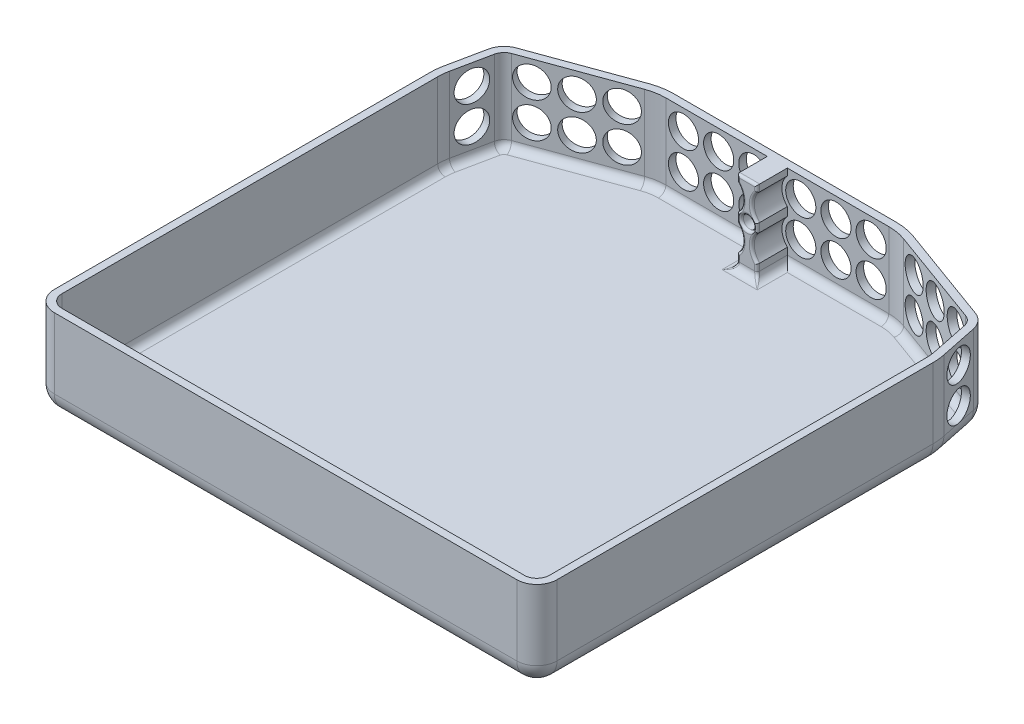
SolidWorks part; units mm, degrees
material "ABS"
ref_plane "Front Plane" through (0, 0, 0) normal (0, 0, 1) x (1, 0, 0)
ref_plane "Top Plane" through (0, 0, 0) normal (0, 1, 0) x (1, 0, 0)
ref_plane "Right Plane" through (0, 0, 0) normal (1, 0, 0) x (0, 0, -1)
sketch "Sketch1" plane through (0, 0, 0) normal (0, 1, 0) x (1, 0, 0)
  line L0 (-100, 0) -> (0, 0) construction
  line L1 (0, 118.6458) -> (-48.563, 118.6458)
  line L2 (-100, 80) -> (-100, -80)
  line L3 (-100, -80) -> (0, -80)
  line L4 (-48.563, 118.6458) -> (-95.5476, 101.5447)
  line L5 (0, 118.6458) -> (0, -80)
  line L7 (-100, 80) -> (-95.5476, 101.5447)
  line L8 (0, -80) -> (0, 118.6458) construction
  point P0 (0, 0)
  dimension "D3" = 191.676
  dimension "D6" = 50
  dimension "D1" = 22
  dimension "D2" = 160
  dimension "D4" = 200
  dimension "D5" = 100
extrude "Boss-Extrude1" add sketch "Sketch1" along normal blind 36
fillet "Fillet4" radius 8 1 edges at (-100, 18, 80)
fillet "Fillet5" radius 24 1 edges at (-100, 18, -80)
fillet "Fillet6" radius 8 1 edges at (-95.5476, 18, -101.5447)
fillet "Fillet7" radius 24 1 edges at (-48.563, 18, -118.6458)
sketch "Sketch2" plane through (0, 0, -118.6458) normal (0, 0, -1) x (-1, 0, 0)
  line L0 (44.3311, 0) -> (44.3311, 36) construction
  line L1 (0, 36) -> (44.3311, 36) construction
  line L2 (9.3311, 14) -> (9.3311, 28) construction
  line L3 (29.3311, 28) -> (31.3311, 28) construction
  line L4 (9.3311, 21) -> (0, 21) construction
  line L5 (0, 36) -> (0, 0) construction
  line L6 (0, 0) -> (44.3311, 0) construction
  circle A0 centre (37.3311, 28) radius 6
  circle A1 centre (23.3311, 28) radius 6
  circle A2 centre (9.3311, 28) radius 6
  circle A3 centre (23.3311, 14) radius 6
  circle A4 centre (9.3311, 14) radius 6
  circle A5 centre (37.3311, 14) radius 6
  circle A6 centre (0, 21) radius 2.5
  dimension "D1" = 12
  dimension "D6" = 5
  dimension "D2" = 7
  dimension "D3" = 8
  dimension "D7" = 21
  dimension "D8" = 14
  dimension "D4" = 3
  dimension "D5" = 2
extrude "Cut-Extrude1" cut sketch "Sketch2" against normal blind 20
sketch "Sketch3" plane through (-43.8128, 0, -120.3747) normal (-0.342, 0, -0.9397) x (-0.9397, 0, 0.342)
  line L0 (9.2869, 36) -> (50.591, 36) construction
  line L1 (9.2869, 36) -> (9.2869, 0) construction
  circle A0 centre (16.2869, 28) radius 6
  circle A1 centre (30.2869, 28) radius 6
  circle A2 centre (44.2869, 28) radius 6
  circle A3 centre (30.2869, 14) radius 6
  circle A4 centre (44.2869, 14) radius 6
  circle A5 centre (16.2869, 14) radius 6
  dimension "D1" = 12
  dimension "D2" = 8
  dimension "D3" = 7
  dimension "D6" = 21
  dimension "D7" = 22
  dimension "D4" = 3
  dimension "D5" = 2
extrude "Cut-Extrude2" cut sketch "Sketch3" against normal blind 10
sketch "Sketch4" plane through (-111.7597, 0, -23.096) normal (-0.9793, 0, -0.2024) x (-0.2024, 0, 0.9793)
  line L0 (-68.1013, 36) -> (-68.1013, 0) construction
  line L1 (-75.6423, 36) -> (-60.5604, 36) construction
  line L2 (-75.6423, 0) -> (-60.5604, 0) construction
  circle A0 centre (-68.1013, 28) radius 6
  circle A1 centre (-68.1013, 14) radius 6
  dimension "D1" = 12
  dimension "D3" = 2
  dimension "D2" = 8
  dimension "D4" = 22
extrude "Cut-Extrude3" cut sketch "Sketch4" against normal blind 10
mirror "Mirror2" of "Cut-Extrude3", "Cut-Extrude2", "Cut-Extrude1", "Fillet7", "Fillet6", "Fillet5", "Fillet4", "Boss-Extrude1"
fillet "Fillet3" radius 8 16 edges at (-100, 0, -2.773) (0, 0, 80) (0, 0, -118.6458) (-71.9462, 0, -110.135) (-97.9772, 0, -89.7881) (-48.4987, 0, -118.2811) (-94.6691, 0, -100.7854) (-99.8755, 0, -79.9873) (-97.6569, 0, 77.6569) (97.6569, 0, 77.6569) (100, 0, -2.773) (99.8755, 0, -79.9873) (97.9772, 0, -89.7881) (94.6691, 0, -100.7854) (71.9462, 0, -110.135) (48.4987, 0, -118.2811)
sketch "Sketch5" plane through (0, 36, 0) normal (0, 1, 0) x (1, 0, 0)
  line L0 (0, 103.6458) -> (0, 118.6458) construction
  line L1 (44.3311, 118.6458) -> (-44.3311, 118.6458) construction
  line L2 (4, 115.6458) -> (4, 103.6458)
  line L3 (4, 103.6458) -> (-4, 103.6458)
  line L4 (-4, 115.6458) -> (-4, 103.6458)
  line L7 (-4, 115.6458) -> (-44.3311, 115.6458)
  line L16 (90.3267, 100.2525) -> (51.5136, 114.3793)
  line L17 (44.3311, 115.6458) -> (-44.3311, 115.6458)
  line L18 (-51.5136, 114.3793) -> (-90.3267, 100.2525)
  line L19 (-93.5131, 96.5659) -> (-96.5654, 81.796)
  line L20 (-97, 77.546) -> (-97, -72)
  line L21 (-92, -77) -> (92, -77)
  line L22 (97, -72) -> (97, 77.546)
  line L23 (96.5654, 81.796) -> (93.5131, 96.5659)
  line L24 (90.3267, 100.2525) -> (51.5136, 114.3793)
  line L25 (44.3311, 115.6458) -> (4, 115.6458)
  line L26 (-51.5136, 114.3793) -> (-90.3267, 100.2525)
  line L27 (-93.5131, 96.5659) -> (-96.5654, 81.796)
  line L28 (-97, 77.546) -> (-97, -72)
  line L29 (-92, -77) -> (92, -77)
  line L30 (97, -72) -> (97, 77.546)
  line L31 (96.5654, 81.796) -> (93.5131, 96.5659)
  arc A16 (51.5136, 114.3793) -> (44.3311, 115.6458) centre (44.3311, 94.6458) ccw
  arc A17 (-44.3311, 115.6458) -> (-51.5136, 114.3793) centre (-44.3311, 94.6458) ccw
  arc A18 (-90.3267, 100.2525) -> (-93.5131, 96.5659) centre (-88.6166, 95.554) ccw
  arc A19 (-96.5654, 81.796) -> (-97, 77.546) centre (-76, 77.546) ccw
  arc A20 (-97, -72) -> (-92, -77) centre (-92, -72) ccw
  arc A21 (92, -77) -> (97, -72) centre (92, -72) ccw
  arc A22 (97, 77.546) -> (96.5654, 81.796) centre (76, 77.546) ccw
  arc A23 (93.5131, 96.5659) -> (90.3267, 100.2525) centre (88.6166, 95.554) ccw
  arc A24 (51.5136, 114.3793) -> (44.3311, 115.6458) centre (44.3311, 94.6458) ccw
  arc A25 (-44.3311, 115.6458) -> (-51.5136, 114.3793) centre (-44.3311, 94.6458) ccw
  arc A26 (-90.3267, 100.2525) -> (-93.5131, 96.5659) centre (-88.6166, 95.554) ccw
  arc A27 (-96.5654, 81.796) -> (-97, 77.546) centre (-76, 77.546) ccw
  arc A28 (-97, -72) -> (-92, -77) centre (-92, -72) ccw
  arc A29 (92, -77) -> (97, -72) centre (92, -72) ccw
  arc A30 (97, 77.546) -> (96.5654, 81.796) centre (76, 77.546) ccw
  arc A31 (93.5131, 96.5659) -> (90.3267, 100.2525) centre (88.6166, 95.554) ccw
  dimension "D2" = 12
  dimension "D3" = 8
  dimension "D1" = 3
extrude "Cut-Extrude4" cut sketch "Sketch5" against normal offset from surface (33 mm away) 3 up to face at (0, 0, -67.0764)
fillet "Fillet8" radius 3 20 edges at (95.0393, 3, -89.181) (96.8911, 3, -79.6821) (97, 3, -2.773) (95.5355, 3, 75.5355) (0, 3, 77) (-95.5355, 3, 75.5355) (-97, 3, -2.773) (-96.8911, 3, -79.6821) (-95.0393, 3, -89.181) (-92.3994, 3, -98.8236) (-70.9201, 3, -107.3159) (-47.9777, 3, -115.3267) (24.1656, 3, -115.6458) (47.9777, 3, -115.3267) (70.9201, 3, -107.3159) (92.3994, 3, -98.8236) (-24.1656, 3, -115.6458) (-4, 3, -109.6458) (0, 3, -103.6458) (4, 3, -109.6458)
sketch "Sketch6" plane through (0, 0, -115.6458) normal (0, 0, 1) x (1, 0, 0)
  arc A0 (-6.6385, 21) -> (-12.0237, 21) centre (-9.3311, 28) ccw
  arc A1 (-4, 30.753) -> (-4, 25.247) centre (-9.3311, 28) ccw construction
  arc A2 (-12.0237, 21) -> (-6.6385, 21) centre (-9.3311, 14) ccw
  arc A3 (6.6385, 21) -> (12.0237, 21) centre (9.3311, 14) ccw
  arc A4 (12.0237, 21) -> (6.6385, 21) centre (9.3311, 28) ccw
  arc A5 (4, 25.247) -> (4, 30.753) centre (9.3311, 28) ccw construction
  arc A6 (4, 11.247) -> (4, 16.753) centre (9.3311, 14) ccw construction
  arc A7 (-4, 16.753) -> (-4, 11.247) centre (-9.3311, 14) ccw construction
  dimension "D1" = 15
extrude "Cut-Extrude5" cut sketch "Sketch6" along normal up to surface (12 mm away) up to face at (-2.5, 21, -103.6458)
fillet "Fillet10" radius 1 14 edges at (4.8787, 3.8787, -102.7671) (-4.8787, 3.8787, -102.7671) (-4, 34.6377, -103.6458) (0, 36, -103.6458) (4, 34.6377, -103.6458) (1.8311, 28, -103.6458) (4, 21, -103.6458) (1.8311, 14, -103.6458) (4, 7.3623, -103.6458) (-4, 7.3623, -103.6458) (-1.8311, 14, -103.6458) (-4, 21, -103.6458) (-1.8311, 28, -103.6458) (-2.5, 21, -103.6458)
